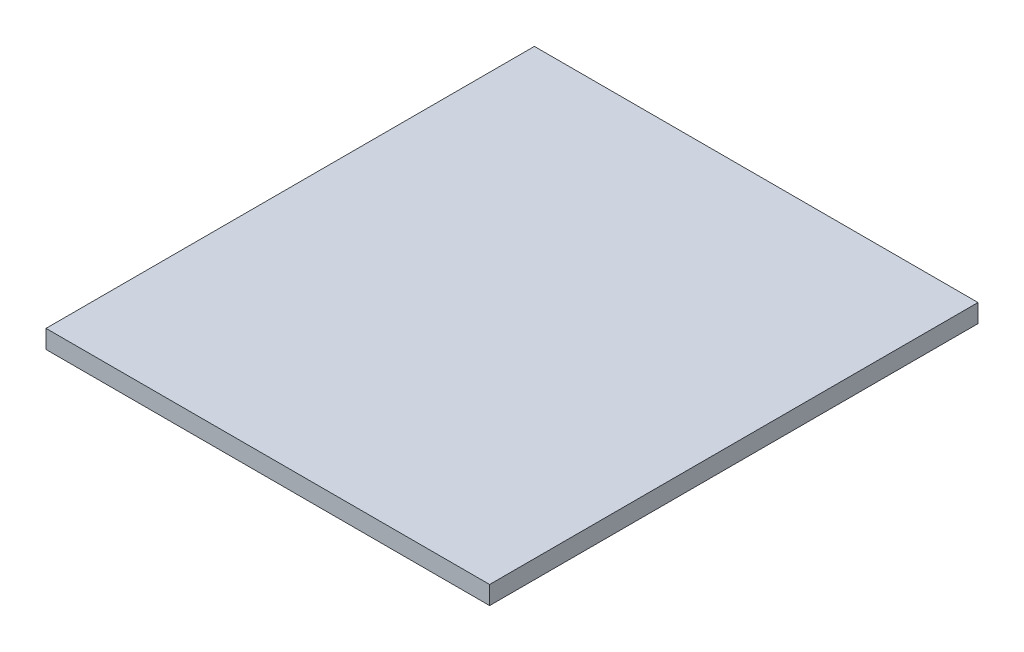
SolidWorks part; units mm, degrees
material "Perspex (TM) GS Acrylic Cast Sheet"
ref_plane "Front Plane" through (0, 0, 0) normal (0, 0, 1) x (1, 0, 0)
ref_plane "Top Plane" through (0, 0, 0) normal (0, 1, 0) x (1, 0, 0)
ref_plane "Right Plane" through (0, 0, 0) normal (1, 0, 0) x (0, 0, -1)
sketch "Sketch1" plane through (0, 0, 0) normal (0, 1, 0) x (1, 0, 0)
  line L1 (-109, -120) -> (109, -120)
  line L2 (-109, -120) -> (-109, 120)
  line L3 (-109, 120) -> (109, 120)
  line L4 (109, -120) -> (109, 120)
  line L5 (-109, -120) -> (109, 120) construction
  line L6 (-109, 120) -> (109, -120) construction
  point P0 (0, 0)
  dimension "D2" = 240
  dimension "D1" = 218
extrude "Boss-Extrude1" add sketch "Sketch1" along normal blind 9
equation "\"PCLength\"= 145mm'Length across I/O from PS to GPU"
equation "\"PCWidth\"= 340mm'Distance of longest part parallel to GPU(ussually GPU)"
equation "\"PCHeight\"= 180mm'Tallest point with mobo laying flat"
equation "\"WallThickness\"= 9mm'Thickness of each outer tank wall"
equation "\"ThermoBarrierThickness\"= 6mm'Thickness of barrier between hot side and cold side"
equation "\"HotSideGap\"= 36mm'Space in the hot side for a pump"
equation "\"PCClearance\"= 30mm'Clearance from top of tank to top of PC"
equation "\"RadiatorHeight\"= 275mm'Final Height from ground of radiators"
equation "\"D2@Sketch1\"=\"PCHeight\" + \"ThermoBarrierThickness\" + \"HotSideGap\" + (2 * \"WallThickness\")"
equation "\"D1@Boss-Extrude1\"=\"WallThickness\""
equation "\"D1@Sketch1\"=\"PCLength\" + (2 * \"WallThickness\") + \"AirflowGap\" + 30"
equation "\"AirflowGap\"= 25mm'Distance between radiators and tank for airflow"
equation "\"VolumeSubtraction\"= 230mm"
